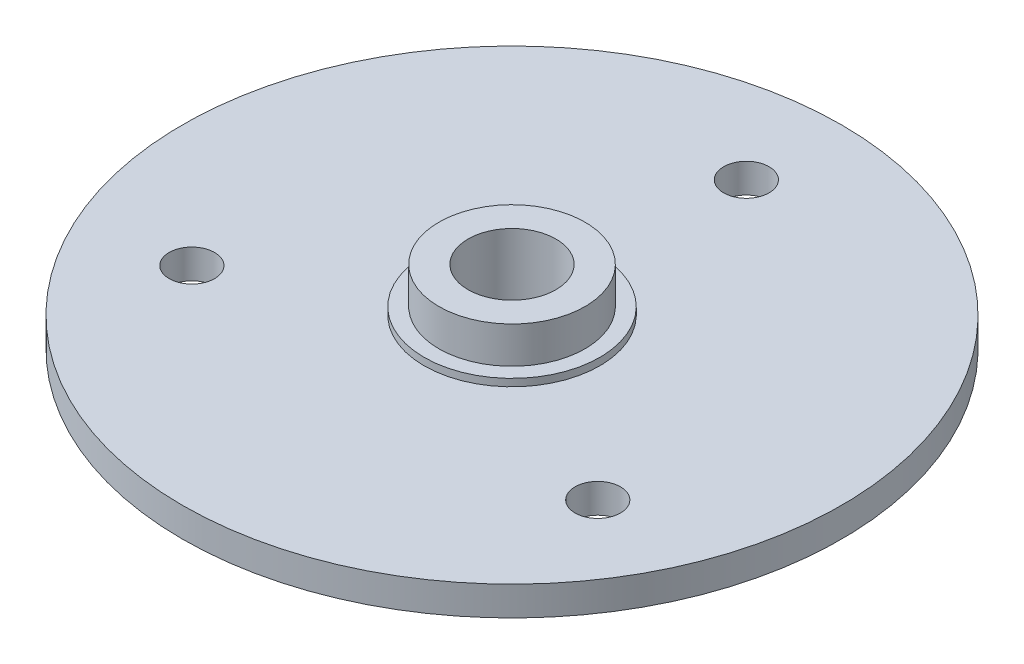
SolidWorks part; units mm, degrees
ref_plane "正面" through (0, 0, 0) normal (0, 0, 1) x (1, 0, 0)
ref_plane "平面" through (0, 0, 0) normal (0, 1, 0) x (1, 0, 0)
ref_plane "右側面" through (0, 0, 0) normal (1, 0, 0) x (0, 0, -1)
sketch "ｽｹｯﾁ1" plane through (0, 0, 0) normal (0, 1, 0) x (1, 0, 0)
  line L0 (0, 0) -> (0, 16) construction
  line L1 (-13.8564, -8) -> (0, 0) construction
  line L2 (0, 0) -> (13.8564, -8) construction
  circle A0 centre (0, 0) radius 22.5
  circle A1 centre (0, 16) radius 1.55
  circle A2 centre (13.8564, -8) radius 1.55
  circle A3 centre (-13.8564, -8) radius 1.55
  dimension "D1" = 45
  dimension "D2" = 16
  dimension "D3" = 3.1
  dimension "D4" = 3
extrude "ﾎﾞｽ - 押し出し1" add sketch "ｽｹｯﾁ1" along normal blind 2
sketch "ｽｹｯﾁ2" plane through (0, 2, 0) normal (0, 1, 0) x (1, 0, 0)
  circle A0 centre (0, 0) radius 4.99
  dimension "D1" = 9.98
extrude "ﾎﾞｽ - 押し出し2" add sketch "ｽｹｯﾁ2" along normal blind 3
sketch "ｽｹｯﾁ3" plane through (0, 2, 0) normal (0, 1, 0) x (1, 0, 0)
  circle A0 centre (0, 0) radius 6
  dimension "D1" = 12
extrude "ﾎﾞｽ - 押し出し3" add sketch "ｽｹｯﾁ3" along normal blind 0.5
sketch "ｽｹｯﾁ4" plane through (0, 5, 0) normal (0, 1, 0) x (1, 0, 0)
  circle A0 centre (0, 0) radius 3
  dimension "D1" = 6
extrude "ｶｯﾄ - 押し出し1" cut sketch "ｽｹｯﾁ4" against normal through all
